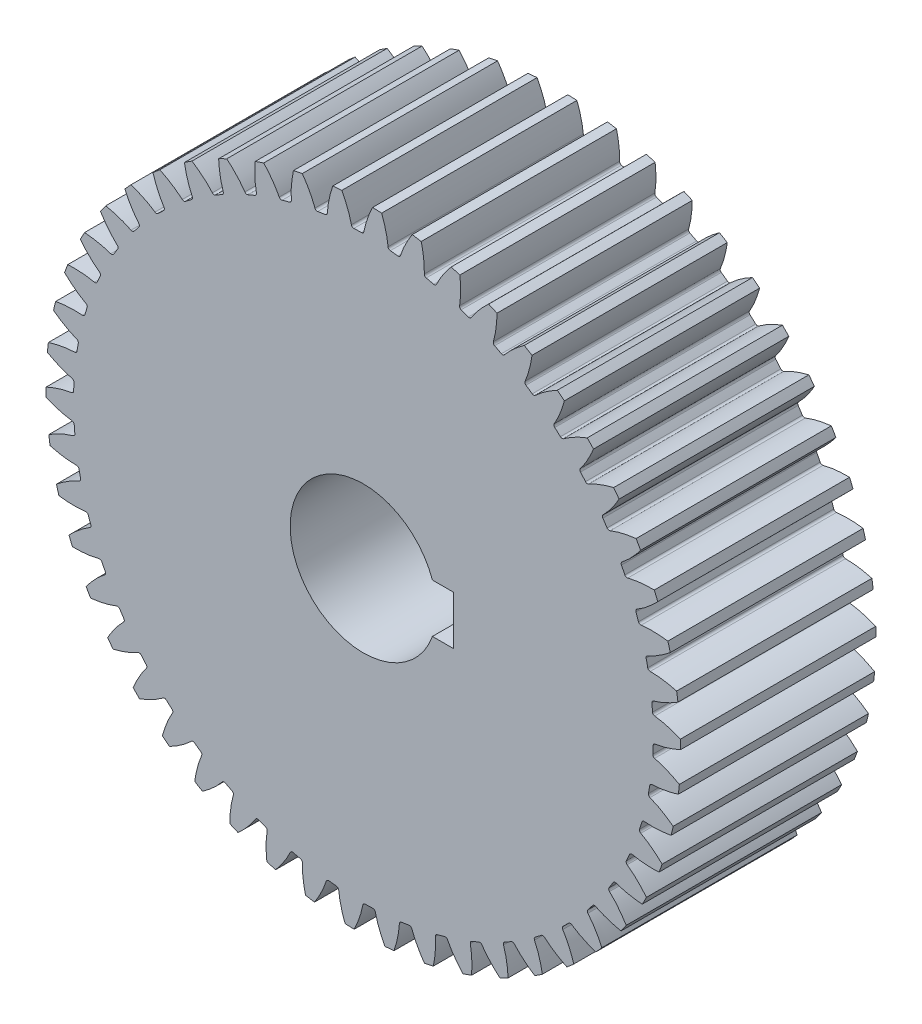
SolidWorks part; units mm, degrees
ref_plane "Front Plane" through (0, 0, 0) normal (0, 0, 1) x (1, 0, 0)
ref_plane "Top Plane" through (0, 0, 0) normal (0, 1, 0) x (1, 0, 0)
ref_plane "Right Plane" through (0, 0, 0) normal (1, 0, 0) x (0, 0, -1)
sketch "Involute Geometry" plane through (0, 0, 0) normal (0, 0, 1) x (1, 0, 0)
  line L0 (0, 23.4923) -> (0, 0) construction
  line L1 (0, 0) -> (1.125, 25.9757) construction
  line L2 (2.031, 23.4044) -> (0, 0) construction
  line L3 (0.3366, 24.9977) -> (0, 0) construction
  line L4 (0, 0) -> (1.8258, 24.9332) construction
  circle A1 centre (0, 0) radius 23.4923 construction
  circle A2 centre (0, 0) radius 25 construction
  circle A3 centre (0, 0) radius 26 construction
  circle A4 centre (0, 0) radius 23.75 construction
  arc A5 (0.7536, 25.9891) -> (1.4961, 25.9569) centre (0, 0) cw
  arc A6 (0.3366, 24.9977) -> (1.8258, 24.9332) centre (0, 0) cw construction
  spline S0 degree 4 poles (0, 23.4923) (0, 23.5114) (0.0013, 23.5648) (0.0089, 23.6656) (0.0287, 23.8296) (0.081, 24.1325) (0.1926, 24.5862) (0.3554, 25.0766) (0.5626, 25.5852) (0.7677, 26.0245) (0.9438, 26.37) (1.171, 26.7822) (1.4642, 27.2682) (1.8332, 27.8211) (2.2875, 28.4323) (2.7797, 29.0321) (3.2982, 29.6089) (3.8411, 30.1634) (4.4053, 30.6951) (4.9175, 31.1416) (5.3665, 31.5096) (5.7503, 31.8087) (6.0572, 32.04) (6.3766, 32.2711) (6.6846, 32.4876) (7.0225, 32.7147) (7.3185, 32.909) (7.7622, 33.1868) (8.0307, 33.348) (8.4647, 33.6019) (8.6612, 33.7084) (8.8384, 33.8077) (8.891, 33.8352) (8.9294, 33.8561) (8.9501, 33.8675) knots 0 0 0 0 0 0.005377 0.015084 0.028532 0.04661 0.092111 0.146842 0.174209 0.201575 0.228941 0.256307 0.307035 0.361767 0.4165 0.471232 0.525964 0.580697 0.635429 0.690161 0.717528 0.744894 0.77226 0.799626 0.826992 0.854358 0.881725 0.909091 0.954545 0.977273 0.988636 0.994318 1 1 1 1 1 construction
  spline S1 degree 4 poles (0, 23.4923) (0, 23.5114) (0.0013, 23.5648) (0.0089, 23.6656) (0.0287, 23.8296) (0.081, 24.1325) (0.1926, 24.5862) (0.3554, 25.0766) (0.5626, 25.5852) (0.7677, 26.0245) (0.9438, 26.37) (1.171, 26.7822) (1.4642, 27.2682) (1.8332, 27.8211) (2.2875, 28.4323) (2.7797, 29.0321) (3.2982, 29.6089) (3.8411, 30.1634) (4.4053, 30.6951) (4.9175, 31.1416) (5.3665, 31.5096) (5.7503, 31.8087) (6.0572, 32.04) (6.3766, 32.2711) (6.6846, 32.4876) (7.0225, 32.7147) (7.3185, 32.909) (7.6041, 33.0878) (7.7558, 33.1811) (7.8311, 33.2268) knots 0 0 0 0 0 0.005377 0.015084 0.028532 0.04661 0.092111 0.146842 0.174209 0.201575 0.228941 0.256307 0.307035 0.361767 0.4165 0.471232 0.525964 0.580697 0.635429 0.690161 0.717528 0.744894 0.77226 0.799626 0.826992 0.854358 0.881725 0.909091 0.909091 0.909091 0.909091 0.909091
  spline S3 degree 4 poles (2.031, 23.4044) (2.0327, 23.4233) (2.036, 23.4767) (2.0371, 23.5778) (2.0316, 23.7428) (2.0056, 24.0491) (1.9337, 24.5108) (1.8139, 25.0134) (1.6514, 25.5381) (1.4851, 25.9934) (1.3395, 26.3529) (1.1488, 26.7831) (0.8988, 27.2927) (0.5789, 27.8754) (0.1792, 28.5237) (-0.2593, 29.1637) (-0.726, 29.7832) (-1.219, 30.3825) (-1.7351, 30.961) (-2.2068, 31.4501) (-2.6223, 31.8556) (-2.9787, 32.1868) (-3.2645, 32.4437) (-3.5628, 32.7016) (-3.8509, 32.9439) (-4.1678, 33.1993) (-4.446, 33.4185) (-4.864, 33.7336) (-5.1175, 33.9174) (-5.528, 34.2079) (-5.7146, 34.331) (-5.8825, 34.4453) (-5.9325, 34.4771) (-5.969, 34.5013) (-5.9886, 34.5144) knots 0 0 0 0 0 0.005377 0.015084 0.028532 0.04661 0.092111 0.146842 0.174209 0.201575 0.228941 0.256307 0.307035 0.361767 0.4165 0.471232 0.525964 0.580697 0.635429 0.690161 0.717528 0.744894 0.77226 0.799626 0.826992 0.854358 0.881725 0.909091 0.954545 0.977273 0.988636 0.994318 1 1 1 1 1 construction
  spline S4 degree 4 poles (2.031, 23.4044) (2.0327, 23.4233) (2.036, 23.4767) (2.0371, 23.5778) (2.0316, 23.7428) (2.0056, 24.0491) (1.9337, 24.5108) (1.8139, 25.0134) (1.6514, 25.5381) (1.4851, 25.9934) (1.3395, 26.3529) (1.1488, 26.7831) (0.8988, 27.2927) (0.5789, 27.8754) (0.1792, 28.5237) (-0.2593, 29.1637) (-0.726, 29.7832) (-1.219, 30.3825) (-1.7351, 30.961) (-2.2068, 31.4501) (-2.6223, 31.8556) (-2.9787, 32.1868) (-3.2645, 32.4437) (-3.5628, 32.7016) (-3.8509, 32.9439) (-4.1678, 33.1993) (-4.446, 33.4185) (-4.7151, 33.6213) (-4.8581, 33.7274) (-4.9292, 33.7794) knots 0 0 0 0 0 0.005377 0.015084 0.028532 0.04661 0.092111 0.146842 0.174209 0.201575 0.228941 0.256307 0.307035 0.361767 0.4165 0.471232 0.525964 0.580697 0.635429 0.690161 0.717528 0.744894 0.77226 0.799626 0.826992 0.854358 0.881725 0.909091 0.909091 0.909091 0.909091 0.909091
  dimension "D5" = 3.417
sketch "Sketch2" plane through (0, 0, 0) normal (0, 0, 1) x (1, 0, 0)
  circle A0 centre (0, 0) radius 23.75 construction
  circle A1 centre (0, 0) radius 23.75
extrude "Boss-Extrude1" add sketch "Sketch2" along normal mid plane 16
sketch "Sketch3" plane through (0, 0, 0) normal (0, 0, 1) x (1, 0, 0)
  arc A3 (0.0199, 23.75) -> (2.0335, 23.6628) centre (0, 0) cw
  arc A4 (1.4961, 25.9569) -> (0.7536, 25.9891) centre (0, 0) ccw construction
  arc A5 (1.4961, 25.9569) -> (0.7536, 25.9891) centre (0, 0) ccw
  circle A7 centre (0, 0) radius 23.75 construction
  spline S0 degree 4 poles (999.8204, 40.2462) (20.7121, 20.125) (0.4503, 21.1025) (-0.1347, 22.474) (0.0287, 23.8296) (0.081, 24.1325) (0.1926, 24.5862) (0.3554, 25.0766) (0.5626, 25.5852) (0.7677, 26.0245) (0.9438, 26.37) (1.171, 26.7822) (1.4642, 27.2682) (1.8332, 27.8211) (2.2875, 28.4323) (2.7797, 29.0321) (3.2982, 29.6089) (3.8411, 30.1634) (4.4053, 30.6951) (4.9175, 31.1416) (5.3665, 31.5096) (5.7503, 31.8087) (6.0572, 32.04) (6.3766, 32.2711) (6.6846, 32.4876) (7.0225, 32.7147) (8.3806, 33.6059) (11.7895, 35.5553) (-19.6779, 16.1915) (862.8738, 551.731) knots -0.338747 -0.338747 -0.338747 -0.338747 -0.338747 0.005377 0.015084 0.028532 0.04661 0.092111 0.146842 0.174209 0.201575 0.228941 0.256307 0.307035 0.361767 0.4165 0.471232 0.525964 0.580697 0.635429 0.690161 0.717528 0.744894 0.77226 0.799626 0.826992 0.854358 0.881725 1.301773 1.301773 1.301773 1.301773 1.301773 only from (0, 23.4923) to (7.5082, 22.3415) construction
  spline S1 degree 4 poles (0.0199, 23.75) (0.0244, 23.7861) (0.0384, 23.8856) (0.0837, 24.1434) (0.1926, 24.5862) (0.3677, 25.1136) (0.5556, 25.5675) (0.6944, 25.8667) (0.7536, 25.9891) knots 0.018251 0.018251 0.018251 0.018251 0.018251 0.028532 0.04661 0.092111 0.146842 0.185208 0.185208 0.185208 0.185208 0.185208
  spline S3 degree 4 poles (-992.5974, 126.5343) (-18.8947, 21.8403) (1.3758, 21.0624) (2.0772, 22.3782) (2.0316, 23.7428) (2.0056, 24.0491) (1.9337, 24.5108) (1.8139, 25.0134) (1.6514, 25.5381) (1.4851, 25.9934) (1.3395, 26.3529) (1.1488, 26.7831) (0.8988, 27.2927) (0.5789, 27.8754) (0.1792, 28.5237) (-0.2593, 29.1637) (-0.726, 29.7832) (-1.219, 30.3825) (-1.7351, 30.961) (-2.2068, 31.4501) (-2.6223, 31.8556) (-2.9787, 32.1868) (-3.2645, 32.4437) (-3.5628, 32.7016) (-3.8509, 32.9439) (-4.1678, 33.1993) (-5.4438, 34.2046) (-8.6715, 36.4414) (21.0041, 14.4296) (-811.9435, 624.2644) knots -0.338747 -0.338747 -0.338747 -0.338747 -0.338747 0.005377 0.015084 0.028532 0.04661 0.092111 0.146842 0.174209 0.201575 0.228941 0.256307 0.307035 0.361767 0.4165 0.471232 0.525964 0.580697 0.635429 0.690161 0.717528 0.744894 0.77226 0.799626 0.826992 0.854358 0.881725 1.301773 1.301773 1.301773 1.301773 1.301773 only from (2.031, 23.4044) to (-4.9292, 33.7794) construction
  spline S4 degree 4 poles (2.0335, 23.6628) (2.0321, 23.6992) (2.0267, 23.7995) (2.0039, 24.0602) (1.9337, 24.5108) (1.8049, 25.0514) (1.6569, 25.5198) (1.5445, 25.8299) (1.4961, 25.9569) knots 0.018251 0.018251 0.018251 0.018251 0.018251 0.028532 0.04661 0.092111 0.146842 0.185208 0.185208 0.185208 0.185208 0.185208
extrude "Boss-Extrude2" add sketch "Sketch3" along normal through all and the other way through all
fillet "Fillet2" radius 0.2 2 edges at (0.0199, 23.75, 0) (2.0335, 23.6628, 0)
pattern_circular "CirPattern1" count 50 over 360 about axis through (0, 0, 8) along (0, 0, -1) of "Boss-Extrude2", "Fillet2"
ref_axis "Axis1" through (0, 0, 8) along (0, 0, -1)
sketch "Sketch4" plane through (0, 0, -8) normal (0, 0, -1) x (-1, 0, 0)
  circle A1 centre (0, 0) radius 6
  dimension "D1" = 12
extrude "Cut-Extrude1" cut sketch "Sketch4" against normal through all
sketch "Sketch5" plane through (0, 0, -8) normal (0, 0, -1) x (-1, 0, 0)
  line L7 (-7.4, -2) -> (-3.4, -2)
  line L8 (-7.4, -2) -> (-7.4, 2)
  line L9 (-7.4, 2) -> (-3.4, 2)
  line L10 (-3.4, -2) -> (-3.4, 2)
  line L11 (-7.4, -2) -> (-3.4, 2) construction
  line L12 (-7.4, 2) -> (-3.4, -2) construction
  circle A3 centre (0, 0) radius 6 construction
  point P7 (-5.4, 0)
  dimension "D1" = 2.6
  dimension "D3" = 4
extrude "Cut-Extrude2" cut sketch "Sketch5" against normal through all
equation "\"N\"= 50'Number of Teeth"
equation "\"m\"= 1mm'Diametral Pitch"
equation "\"phi\"= 20deg'Pressure Angle"
equation "\"a\"= \"m\"'Addendum"
equation "\"b\"= 1.25 * \"m\"'Dedendum"
equation "\"Dp\"= \"N\" * \"m\"'Pitch diameter"
equation "\"Db\"= \"Dp\" * cos ( \"phi\" )'Base diameter"
equation "\"D1@Involute Geometry\" = \"Db\""
equation "\"D2@Involute Geometry\" = \"Dp\""
equation "\"D3@Involute Geometry\" = \"Dp\" + 2 * \"a\""
equation "\"D4@Involute Geometry\" = \"Dp\" - 2 * \"b\""
equation "\"D1@CirPattern1\"=\"N\""
equation "\"D5@Involute Geometry\"=180/\"N\"-\"j_th\"/2"
equation "\"D1@Boss-Extrude1\"=16*\"m\""
equation "\"j_th\"= ( 360deg ) * ( 0.16mm ) / ( pi * \"Dp\" )'Angular backlash"
equation "\"alpha\"= sqr ( \"Dp\" ^ 2 - \"Db\" ^ 2 ) / \"Db\" * 180 / pi - \"phi\""
equation "\"beta\"= ( ( 360deg / \"N\" ) / 4 - \"alpha\" )"
